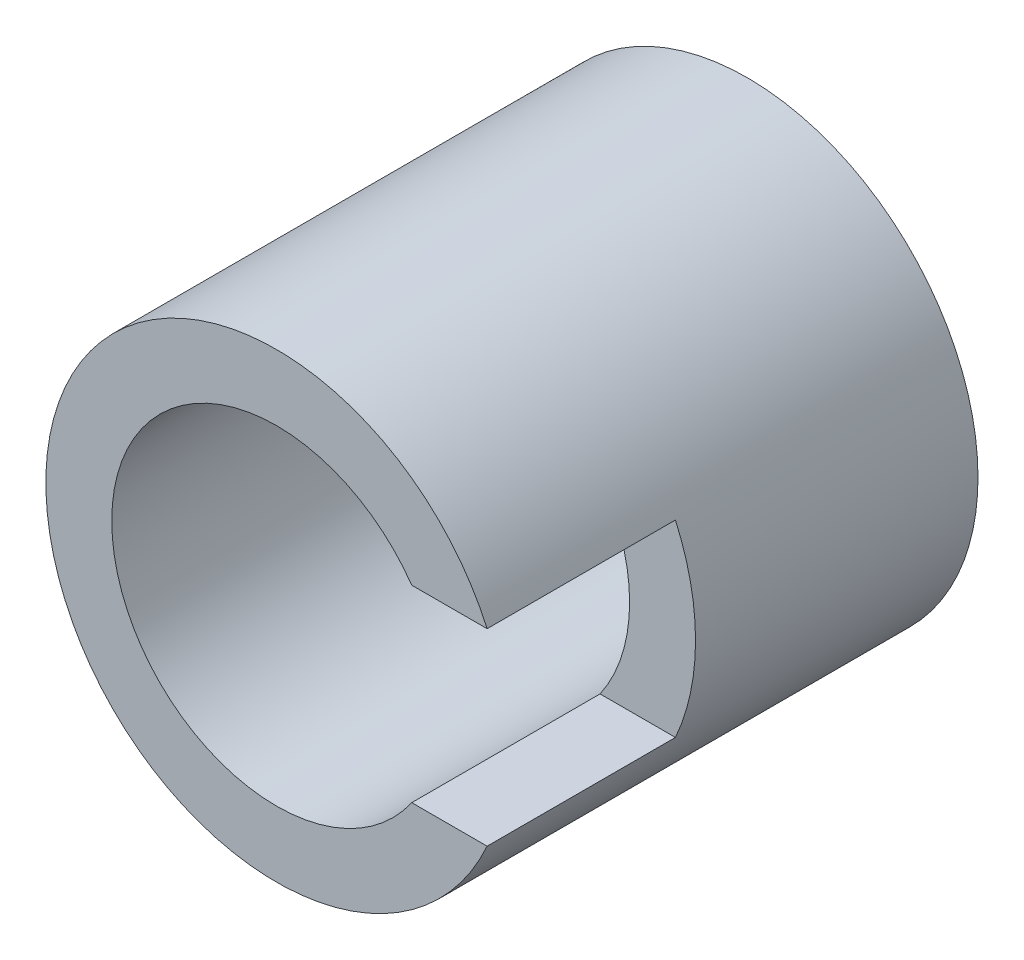
SolidWorks part; units mm, degrees
ref_plane "前视基准面" through (0, 0, 0) normal (0, 0, 1) x (1, 0, 0)
ref_plane "上视基准面" through (0, 0, 0) normal (0, 1, 0) x (1, 0, 0)
ref_plane "右视基准面" through (0, 0, 0) normal (1, 0, 0) x (0, 0, -1)
other "Configuration Table"
sketch "草图1" plane through (0, 0, 0) normal (0, 0, 1) x (1, 0, 0)
  circle A0 centre (0, 0) radius 3.5
  circle A1 centre (0, 0) radius 4.9
  dimension "D1" = 7
  dimension "D2" = 9.8
extrude "凸台-拉伸1" add sketch "草图1" along normal blind 10
sketch "草图2" plane through (0, 0, 10) normal (0, 0, 1) x (1, 0, 0)
  line L1 (-0.9157, -2) -> (6.1633, -2)
  line L2 (-0.9157, -2) -> (-0.9157, 2)
  line L3 (-0.9157, 2) -> (6.1633, 2)
  line L4 (6.1633, -2) -> (6.1633, 2)
  line L5 (-0.9157, -2) -> (6.1633, 2) construction
  line L6 (-0.9157, 2) -> (6.1633, -2) construction
  point P0 (2.6238, 0)
  point P5 (0, 0)
  dimension "D1" = 4
extrude "切除-拉伸1" cut sketch "草图2" against normal blind 4
